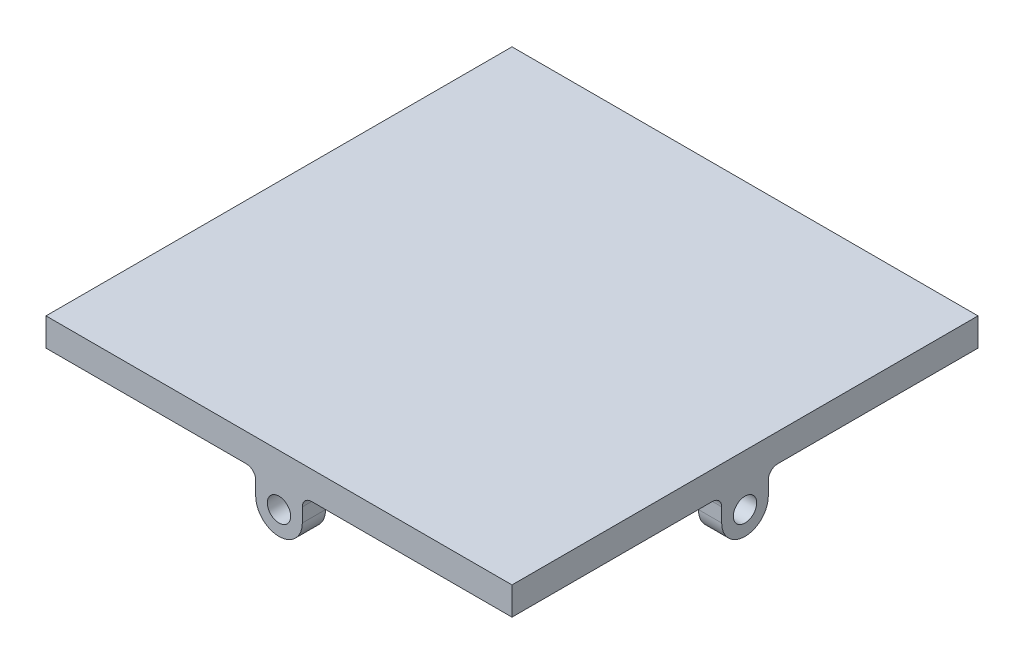
SolidWorks part; units mm, degrees
ref_plane "Plano frontal" through (0, 0, 0) normal (0, 0, 1) x (1, 0, 0)
ref_plane "Plano superior" through (0, 0, 0) normal (0, 1, 0) x (1, 0, 0)
ref_plane "Plano direito" through (0, 0, 0) normal (1, 0, 0) x (0, 0, -1)
sketch "Esboço1" plane through (0, 0, 0) normal (0, 1, 0) x (1, 0, 0)
  line L1 (0, 0) -> (500, 0)
  line L2 (0, 0) -> (0, 500)
  line L3 (0, 500) -> (500, 500)
  line L4 (500, 0) -> (500, 500)
  dimension "D1" = 500
extrude "Ressalto-extrusão1" add sketch "Esboço1" along normal blind 30
sketch "Esboço2" plane through (0, 0, 0) normal (0, -1, 0) x (1, 0, 0)
  line L0 (0, -500) -> (0, 0) construction
  line L1 (225, -25) -> (275, -25)
  line L2 (225, -25) -> (225, 0)
  line L3 (225, 0) -> (275, 0)
  line L4 (275, -25) -> (275, 0)
  line L5 (0, 0) -> (500, 0) construction
  line L6 (500, 0) -> (500, -500) construction
  line L7 (475, -225) -> (500, -225)
  line L9 (500, -500) -> (0, -500) construction
  line L14 (475, -225) -> (475, -275)
  line L15 (475, -275) -> (500, -275)
  line L16 (500, -225) -> (500, -275)
  line L22 (0, -225) -> (0, -275)
  line L23 (25, -275) -> (0, -275)
  line L24 (25, -225) -> (25, -275)
  line L25 (25, -225) -> (0, -225)
  line L26 (275, -475) -> (275, -500)
  line L27 (225, -500) -> (275, -500)
  line L28 (225, -475) -> (225, -500)
  line L29 (225, -475) -> (275, -475)
  point P6 (250, 0)
  point P21 (500, -250)
  dimension "D1" = 250
  dimension "D2" = 50
  dimension "D3" = 25
  dimension "D4" = 0
  dimension "D5" = 250
  dimension "D6" = 50
  dimension "D7" = 25
  dimension "D8" = 0
extrude "Ressalto-extrusão2" add sketch "Esboço2" along normal blind 50
sketch "Esboço3" plane through (0, 0, 0) normal (-1, 0, 0) x (0, 0, 1)
  line L3 (-225, -50) -> (-275, -50) construction
  line L4 (-275, -50) -> (-275, 0) construction
  circle A0 centre (-250, -25) radius 12.5
  point P2 (-240.4997, 22.8439)
  dimension "D3" = 25
  dimension "D1" = 25
  dimension "D2" = 25
extrude "Corte-extrusão1" cut sketch "Esboço3" against normal through all
sketch "Esboço4" plane through (0, 0, 0) normal (0, 0, 1) x (1, 0, 0)
  line L0 (275, -50) -> (275, 0) construction
  line L1 (0, 0) -> (225, 0) construction
  circle A0 centre (250, -25) radius 12.5
  dimension "D3" = 25
  dimension "D1" = 25
  dimension "D2" = 25
extrude "Corte-extrusão2" cut sketch "Esboço4" against normal through all
fillet "Filete1" radius 25 8 edges at (275, -50, -487.5) (225, -50, -487.5) (12.5, -50, -275) (12.5, -50, -225) (487.5, -50, -275) (487.5, -50, -225) (275, -50, -12.5) (225, -50, -12.5)
fillet "Filete4" radius 10 8 edges at (487.5, 0, -275) (487.5, 0, -225) (275, 0, -12.5) (225, 0, -12.5) (12.5, 0, -225) (275, 0, -487.5) (225, 0, -487.5) (12.5, 0, -275)
sketch "Esboço5" plane through (0, 0, 0) normal (0, -1, 0) x (1, 0, 0)
  line L0 (25, -285) -> (25, -215) construction
  line L1 (50, -25) -> (450, -25)
  line L2 (25, -50) -> (25, -450)
  line L3 (50, -475) -> (450, -475)
  line L4 (475, -50) -> (475, -450)
  line L6 (215, -25) -> (285, -25) construction
  line L7 (475, -215) -> (475, -285) construction
  line L8 (285, -475) -> (215, -475) construction
  line L9 (25, -450) -> (50, -475)
  line L10 (450, -475) -> (475, -450)
  line L11 (25, -50) -> (50, -25)
  line L12 (450, -25) -> (475, -50)
  point P0 (25, -25)
  point P1 (475, -475)
  point P2 (25, -475)
  point P3 (475, -25)
extrude "Corte-extrusão3" cut sketch "Esboço5" against normal blind 15
